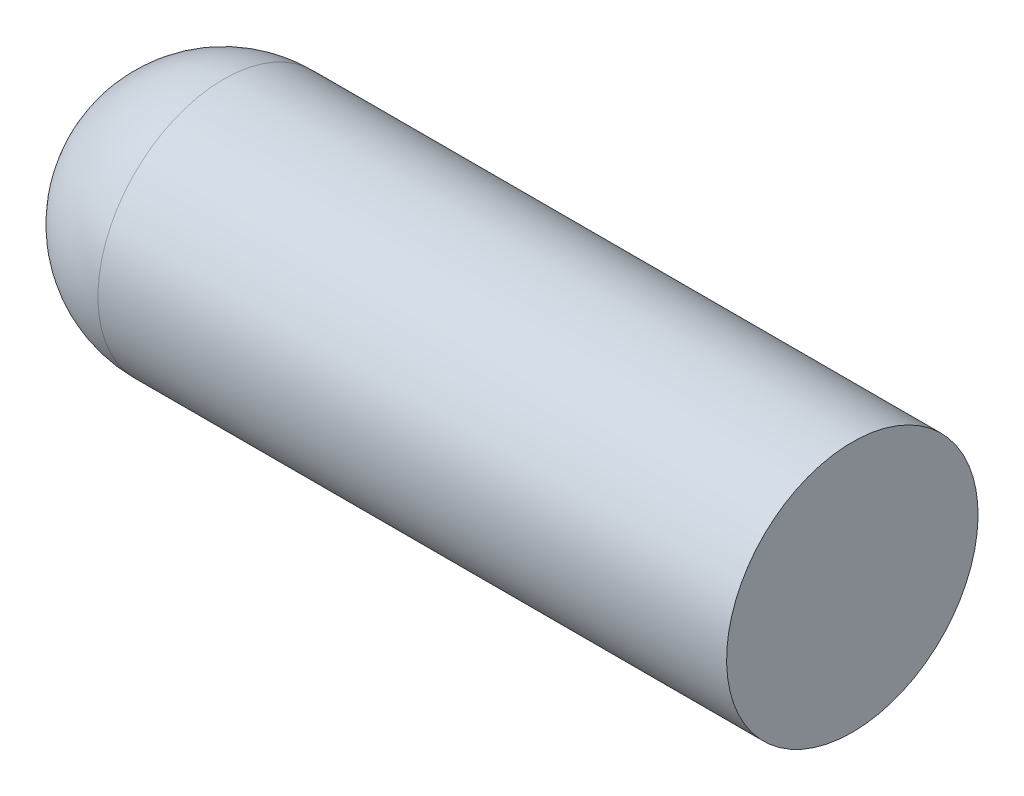
SolidWorks part; units mm, degrees
ref_plane "Front Plane" through (0, 0, 0) normal (0, 0, 1) x (1, 0, 0)
ref_plane "Top Plane" through (0, 0, 0) normal (0, 1, 0) x (1, 0, 0)
ref_plane "Right Plane" through (0, 0, 0) normal (1, 0, 0) x (0, 0, -1)
sketch "Sketch8" plane through (0, 0, 0) normal (0, 0, 1) x (1, 0, 0)
  line L10 (508, 0) -> (0, 0)
  line L12 (508, 78.359) -> (762, 78.359)
  line L14 (508, 0) -> (762, 0)
  line L15 (762, 78.359) -> (762, 0)
  spline S0 degree 4 poles (0, 0) (0.0028, 0.0112) (0.0101, 0.033) (0.0315, 0.074) (0.0698, 0.1316) (0.1192, 0.1954) (0.1898, 0.2761) (0.2748, 0.3639) (0.4019, 0.4843) (0.6026, 0.6567) (0.9144, 0.8984) (1.4448, 1.2671) (2.3422, 1.8219) (3.9262, 2.6864) (6.7922, 4.0534) (11.8911, 6.1625) (20.4311, 9.2161) (31.8916, 12.777) (45.6257, 16.595) (64.7152, 21.4391) (87.8428, 26.7555) (115.2609, 32.4758) (146.9821, 38.4855) (178.7896, 44.0179) (210.6663, 49.1356) (242.6009, 53.8775) (274.5859, 58.2664) (306.6159, 62.3133) (338.6872, 66.0193) (370.7971, 69.3748) (402.9439, 72.3578) (431.1037, 74.6062) (455.263, 76.2292) (474.4437, 77.278) (487.1031, 77.8359) (497.2672, 78.1744) (503.3998, 78.31) (506.4665, 78.3534) (508, 78.359) knots 0 0 0 0 0 0.000089 0.000179 0.000357 0.000536 0.000714 0.001009 0.001304 0.001892 0.002764 0.004066 0.006308 0.010067 0.016745 0.028668 0.049063 0.080344 0.109747 0.139151 0.201713 0.264275 0.326836 0.389398 0.45196 0.514521 0.577083 0.639645 0.702206 0.764768 0.82733 0.889891 0.921172 0.952453 0.976227 0.988113 1 1 1 1 1 construction
  spline S1 degree 4 poles (0, 0) (0.0028, 0.0112) (0.0101, 0.033) (0.0315, 0.074) (0.0698, 0.1316) (0.1192, 0.1954) (0.1898, 0.2761) (0.2748, 0.3639) (0.4019, 0.4843) (0.6026, 0.6567) (0.9144, 0.8984) (1.4448, 1.2671) (2.3422, 1.8219) (3.9262, 2.6864) (6.7922, 4.0534) (11.8911, 6.1625) (20.4311, 9.2161) (31.8916, 12.777) (45.6257, 16.595) (64.7152, 21.4391) (87.8428, 26.7555) (115.2609, 32.4758) (146.9821, 38.4855) (178.7896, 44.0179) (210.6663, 49.1356) (242.6009, 53.8775) (274.5859, 58.2664) (306.6159, 62.3133) (338.6872, 66.0193) (370.7971, 69.3748) (402.9439, 72.3578) (431.1037, 74.6062) (455.263, 76.2292) (474.4437, 77.278) (487.1031, 77.8359) (497.2672, 78.1744) (503.3998, 78.31) (506.4665, 78.3534) (508, 78.359) knots 0 0 0 0 0 0.000089 0.000179 0.000357 0.000536 0.000714 0.001009 0.001304 0.001892 0.002764 0.004066 0.006308 0.010067 0.016745 0.028668 0.049063 0.080344 0.109747 0.139151 0.201713 0.264275 0.326836 0.389398 0.45196 0.514521 0.577083 0.639645 0.702206 0.764768 0.82733 0.889891 0.921172 0.952453 0.976227 0.988113 1 1 1 1 1
  dimension "D1" = 78.359
  dimension "D2" = 254
  dimension "D3" = 78.359
  dimension "D4" = 508
revolve "Revolve8" add sketch "Sketch8" angle 360 about L10
sketch "Sketch9" plane through (0, 0, 0) normal (0, 0, 1) x (1, 0, 0)
  line L0 (-762, 0) -> (3810, 0)
  line L3 (0, 762) -> (3810, 762)
  line L4 (3810, 0) -> (3810, 762)
  line L5 (0, 762) -> (0, -762) construction
  arc A0 (0, 762) -> (-762, 0) centre (0, 0) ccw
  dimension "D1" = 762
revolve "Revolve9" add sketch "Sketch9" angle 360 about L0
combine bodies "Combine1" operation type subtract main body 110 bodies to subtract 108
curve "Curve1"
sketch "Sketch9<3>" plane through (0, 0, 0) normal (0, 0, 1) x (1, 0, 0) same geometry as "Sketch9"
